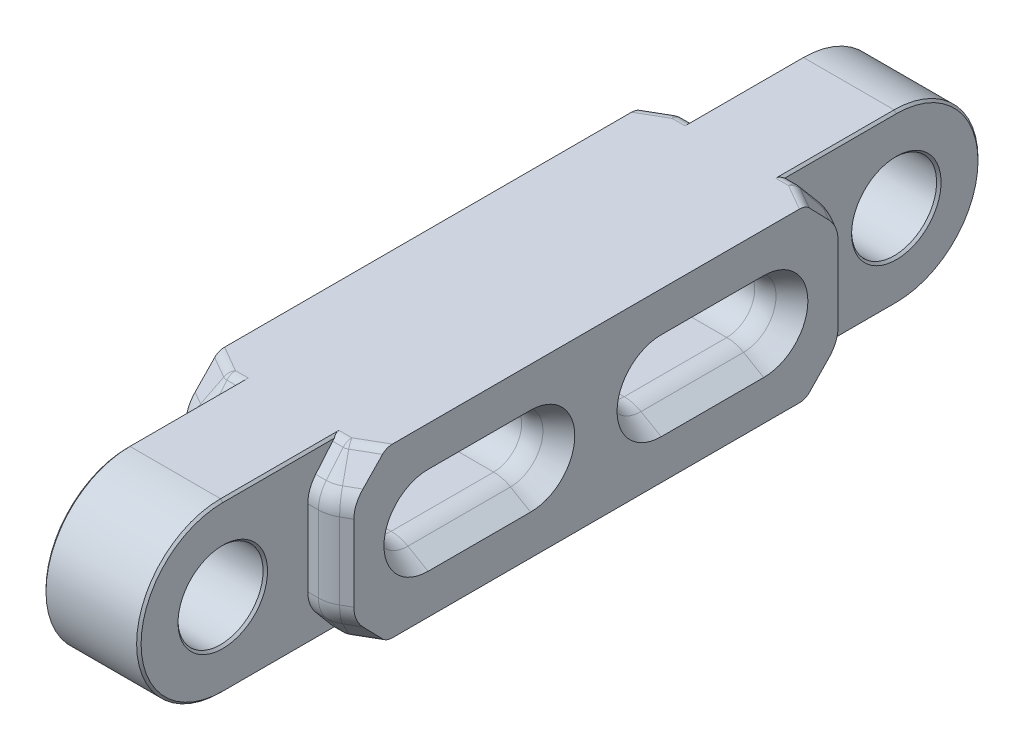
SolidWorks part; units mm, degrees
ref_plane "Front Plane" through (0, 0, 0) normal (1, 0, 0) x (0, 1, 0)
ref_plane "Top Plane" through (0, 0, 0) normal (0, 0, 1) x (0, 1, 0)
ref_plane "Right Plane" through (0, 0, 0) normal (0, 1, 0) x (-1, 0, 0)
sketch "Sketch1" plane through (0, 0, 0) normal (1, 0, 0) x (0, 1, 0)
  line L0 (-15, 0) -> (-15, -120.4)
  line L1 (-15, -60.2) -> (15, -60.2) construction
  line L2 (15, -120.4) -> (15, 0)
  line L3 (-5, -30.2) -> (-5, -48.5333)
  line L4 (-15, -105.2) -> (15, -105.2)
  line L6 (-15, -15.2) -> (15, -15.2)
  line L7 (0, 15) -> (0, -60.2)
  circle A0 centre (0, 0) radius 7.6
  circle A1 centre (0, 0) radius 15
  circle A26 centre (0, -120.4) radius 15
  circle A27 centre (0, -120.4) radius 7.6
  circle A28 centre (0, -48.5333) radius 5
  circle A29 centre (0, -30.2) radius 5
  point P16 (-5, -48.5333)
  point P17 (0, -53.5333)
  point P20 (0, -25.2)
  dimension "D1" = 30
  dimension "D2" = 15.2
  dimension "D3" = 15.2
  dimension "D4" = 90
  dimension "D5" = 10
  dimension "D6" = 6.6667
  dimension "D7" = 10
extrude "Boss-Extrude1" add sketch "Sketch1" along normal blind 8.5 contours L7 A1 A0 | A1 L0 L6 L7 | L0 L1 L7 L6 region at (0, -11.4068, -11.8513) region at (0, -10.3694, 10.3694) region at (0, -8.7306, -37.2989)
extrude "Boss-Extrude2" add sketch "Sketch1<4>" along normal blind 15 contours L0 L1 L7 L6 region at (0, -8.7306, -37.2989)
sketch "Sketch1<4>" plane through (0, 0, 0) normal (1, 0, 0) x (0, 1, 0) same geometry as "Sketch1"
chamfer "Chamfer8" distance 3 angle 30 1 edges at (15, -7.5, -15.2) first distance on face at (11.75, -7.5, -15.2)
fillet "Fillet6" radius 6 1 edges at (12, -7.5, -15.2)
chamfer "Chamfer9" distance 6 angle 40 3 edges at (14.1962, -15, -16.4679) (11.9452, -15, -15.4044) (9.4462, -15, -15.2) first distance on face at (14.1962, -7.5, -16.4679) first distance on face at (11.9188, -7.5, -15.5032) first distance on face at (9.4462, -7.5, -15.2)
fillet "Fillet7" radius 6 3 edges at (14.1962, -9, -16.4679) (11.9452, -9, -15.4044) (9.4462, -9, -15.2)
chamfer "Chamfer10" distance 5 angle 30 3 edges at (15, -3.5355, -52.0689) (15, -5, -39.3667) (15, -3.5355, -26.6645) first distance on face at (7.5, -3.0178, -51.5511) first distance on face at (7.5, -5, -39.3667) first distance on face at (7.5, -3.0178, -27.1822)
fillet "Fillet8" radius 6 3 edges at (10, -3.5355, -52.0689) (10, -5, -39.3667) (10, -3.5355, -26.6645)
fillet "Fillet9" radius 2 3 edges at (9.4462, -15, -20.2346) (10.6422, -15, -20.2675) (12.9375, -15, -21.5547)
chamfer "Chamfer11" distance 0.4 angle 45 3 edges at (8.5, -7.6, 0) (8.5, -15, -10.5836) (8.5, -10.6066, 10.6066)
mirror "Mirror1" about plane through (8.5, 0, 0) normal (0, 1, 0) of bodies 102
mirror "Mirror2" about plane through (8.5, 0, -60.2) normal (0, 0, 1) of bodies 108
mirror "Mirror3" about plane through (0, 0, 0) normal (1, 0, 0) of bodies 109
equation "\"D6@Sketch1\"=\"D5@Sketch1\"*2/3"
equation "\"D7@Sketch1\"=\"D5@Sketch1\""
